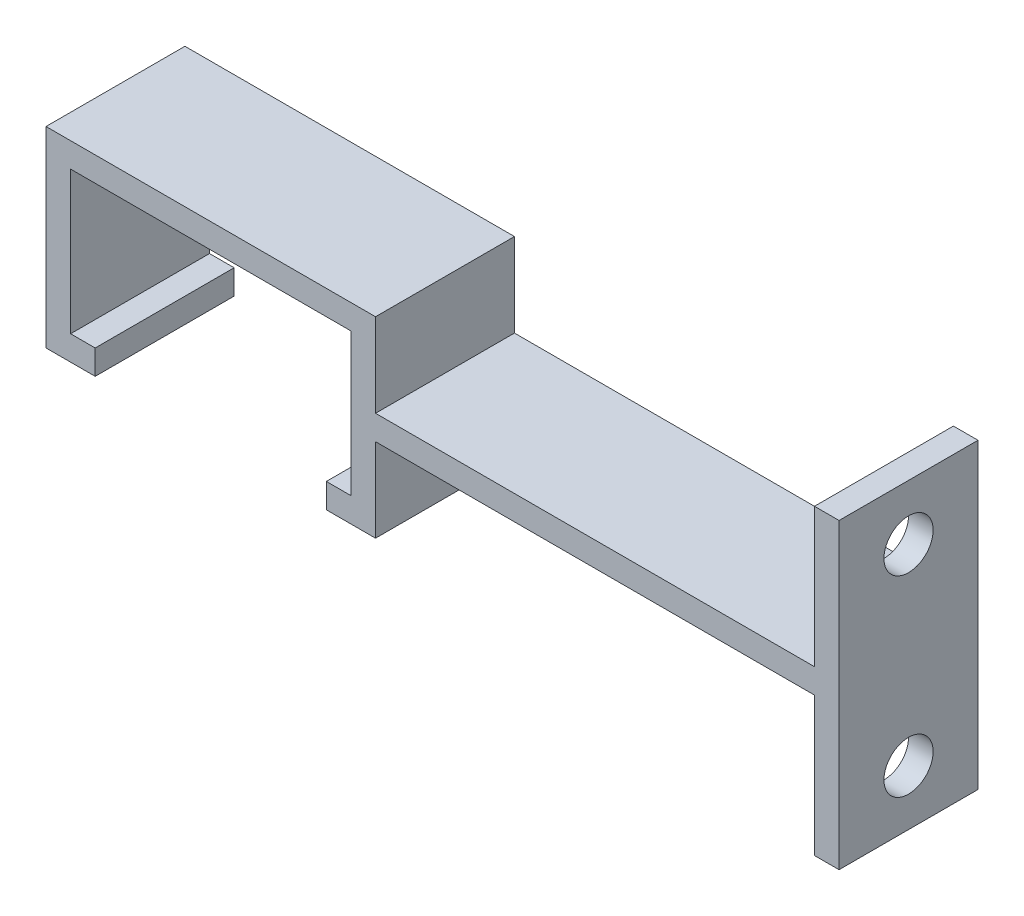
SolidWorks part; units mm, degrees
ref_plane "Plan de face" through (0, 0, 0) normal (0, 0, 1) x (1, 0, 0)
ref_plane "Plan de dessus" through (0, 0, 0) normal (0, 1, 0) x (1, 0, 0)
ref_plane "Plan de droite" through (0, 0, 0) normal (1, 0, 0) x (0, 0, -1)
sketch "Esquisse1" plane through (0, 0, 0) normal (0, 0, 1) x (1, 0, 0)
  line L0 (-21.8, 1) -> (-21.8, 0)
  line L1 (0, 0) -> (-3, 0)
  line L2 (0, 0) -> (0, 13.6)
  line L3 (0, 13.6) -> (-24.8, 13.6)
  line L4 (-24.8, 0) -> (-24.8, 13.6)
  line L5 (-23.8, 12.6) -> (-1, 12.6)
  line L6 (-23.8, 12.6) -> (-23.8, 1)
  line L7 (-23.8, 1) -> (-21.8, 1)
  line L8 (-1, 12.6) -> (-1, 1)
  line L9 (-3, 1) -> (-3, 0)
  line L10 (-3, 1) -> (-1, 1)
  line L11 (-21.8, 0) -> (-24.8, 0)
  dimension "D1" = 13.6
  dimension "D2" = 24.8
  dimension "D3" = 1
  dimension "D4" = 1
  dimension "D5" = 1
  dimension "D6" = 1
  dimension "D7" = 3
  dimension "D8" = 3
extrude "Boss.-Extru.1" add sketch "Esquisse1" along normal blind 11.3
sketch "Esquisse2" plane through (0, 13.6, 0) normal (0, 1, 0) x (1, 0, 0)
  line L0 (0, -11.3) -> (-24.8, -11.3) construction
  line L1 (-16.8, 0) -> (-8, 0)
  line L2 (-16.8, 0) -> (-16.8, -11.3)
  line L3 (-16.8, -11.3) -> (-8, -11.3)
  line L4 (-8, 0) -> (-8, -11.3)
  line L5 (-24.8, -11.3) -> (-24.8, 0) construction
  line L6 (0, -11.3) -> (0, 0) construction
  dimension "D1" = 8
  dimension "D2" = 8
  dimension "D3" = 11.3
extrude "Boss.-Extru.2" add sketch "Esquisse2" along normal blind 1
sketch "Esquisse8" plane through (-8, 0, 0) normal (1, 0, 0) x (0, 0, -1)
  line L1 (-11.3, 13.6) -> (0, 13.6)
  line L2 (-11.3, 13.6) -> (-11.3, 14.6)
  line L3 (-11.3, 14.6) -> (0, 14.6)
  line L4 (0, 13.6) -> (0, 14.6)
  dimension "D1" = 11.3
extrude "Boss.-Extru.5" add sketch "Esquisse8" along normal blind 10
sketch "Esquisse9" plane through (0, 13.6, 0) normal (0, -1, 0) x (1, 0, 0)
  line L1 (2, 11.3) -> (0, 11.3)
  line L2 (2, 11.3) -> (2, 0)
  line L3 (2, 0) -> (0, 0)
  line L4 (0, 11.3) -> (0, 0)
extrude "Boss.-Extru.6" add sketch "Esquisse9" along normal blind 7.8
sketch "Esquisse10" plane through (2, 0, 0) normal (1, 0, 0) x (0, 0, -1)
  line L0 (0, 5.8) -> (0, 0) construction
  line L1 (-11.3, 5.8) -> (0, 5.8)
  line L2 (-11.3, 5.8) -> (-11.3, 7.8)
  line L3 (-11.3, 7.8) -> (0, 7.8)
  line L4 (0, 5.8) -> (0, 7.8)
  dimension "D1" = 2
extrude "Boss.-Extru.7" add sketch "Esquisse10" along normal blind 36.7
sketch "Esquisse11" plane through (0, 5.8, 0) normal (0, -1, 0) x (1, 0, 0)
  line L0 (38.7, 11.3) -> (0, 11.3) construction
  line L1 (38.7, 0) -> (36.7, 0)
  line L2 (38.7, 0) -> (38.7, 11.3)
  line L3 (38.7, 11.3) -> (36.7, 11.3)
  line L4 (36.7, 0) -> (36.7, 11.3)
  dimension "D1" = 2
extrude "Boss.-Extru.8" add sketch "Esquisse11" along normal blind 11.3
sketch "Esquisse12" plane through (0, 7.8, 0) normal (0, 1, 0) x (1, 0, 0)
  line L0 (38.7, 0) -> (2, 0) construction
  line L1 (38.7, -11.3) -> (36.7, -11.3)
  line L2 (38.7, -11.3) -> (38.7, 0)
  line L3 (38.7, 0) -> (36.7, 0)
  line L4 (36.7, -11.3) -> (36.7, 0)
  dimension "D1" = 2
extrude "Boss.-Extru.9" add sketch "Esquisse12" along normal blind 11.3
sketch "Esquisse13" plane through (0, 0, 11.3) normal (0, 0, 1) x (1, 0, 0)
  line L0 (-16.8, 14.6) -> (-25.8, 14.6)
  line L1 (-25.8, 14.6) -> (-25.8, 0)
  line L2 (-25.8, 0) -> (-24.8, 0)
  line L3 (-24.8, 13.6) -> (-24.8, 0) construction
  line L4 (-16.8, 13.6) -> (-24.8, 13.6) construction
  line L6 (-24.8, 0) -> (-24.8, 13.6)
  line L7 (-24.8, 13.6) -> (-16.8, 13.6)
  line L8 (-16.8, 13.6) -> (-16.8, 14.6)
  dimension "D1" = 1
  dimension "D2" = 1
extrude "Boss.-Extru.10" add sketch "Esquisse13" against normal up to vertex (11.3 mm away) up to point (-24.8, 0, 0)
sketch "Esquisse14" plane through (0, 5.8, 0) normal (0, -1, 0) x (1, 0, 0)
  line L0 (0, 11.3) -> (1, 11.3)
  line L1 (36.7, 11.3) -> (0, 11.3) construction
  line L2 (1, 11.3) -> (1, 0)
  line L3 (0, 0) -> (36.7, 0) construction
  line L4 (1, 0) -> (0, 0)
  line L5 (0, 0) -> (0, 11.3)
  dimension "D1" = 1
extrude "Boss.-Extru.11" add sketch "Esquisse14" along normal up to vertex (5.8 mm away) up to point (0, 0, 0)
sketch "Esquisse16" plane through (2, 0, 0) normal (1, 0, 0) x (0, 0, -1)
  line L0 (-11.3, 14.6) -> (0, 14.6)
  line L1 (0, 14.6) -> (0, 7.8)
  line L2 (0, 7.8) -> (-11.3, 7.8)
  line L3 (-11.3, 7.8) -> (-11.3, 14.6)
extrude "Enlèv. mat.-Extru.1" cut sketch "Esquisse16" against normal blind 1
sketch "Esquisse19" plane through (38.7, 0, 0) normal (1, 0, 0) x (0, 0, -1)
  line L1 (-11.3, 19.1) -> (-11.3, -5.5) construction
  line L2 (-11.3, 19.1) -> (0, 19.1) construction
  line L3 (-11.3, 6.8) -> (0, 6.8) construction
  line L4 (0, -5.5) -> (0, 19.1) construction
  line L5 (0, -5.5) -> (-11.3, -5.5) construction
  circle A0 centre (-5.65, 14.6) radius 2
  circle A1 centre (-5.65, -1) radius 2
  point P2 (-5.5167, -5.5)
  point P3 (0, 0)
  dimension "D1" = 4
  dimension "D4" = 5.65
  dimension "D5" = 4
  dimension "D2" = 4.5
  dimension "D3" = 4.5
  dimension "D6" = 5.65
extrude "Enlèv. mat.-Extru.3" cut sketch "Esquisse19" against normal blind 10
sketch "Esquisse22" plane through (0, 0, 11.3) normal (0, 0, 1) x (1, 0, 0)
  line L0 (-25.8, 0) -> (-25.8, -1)
  line L3 (1, 0) -> (-3, 0)
  line L4 (1, 0) -> (1, -1)
  line L5 (1, -1) -> (-3, -1)
  line L6 (-21.8, 0) -> (-21.8, -1)
  line L7 (-3, 0) -> (-3, -1)
  line L8 (-21.8, 0) -> (-25.8, 0)
  line L9 (-21.8, -1) -> (-25.8, -1)
  dimension "D1" = 1
extrude "Boss.-Extru.12" add sketch "Esquisse22" against normal up to vertex (11.3 mm away) up to point (-21.8, 0, 0)
